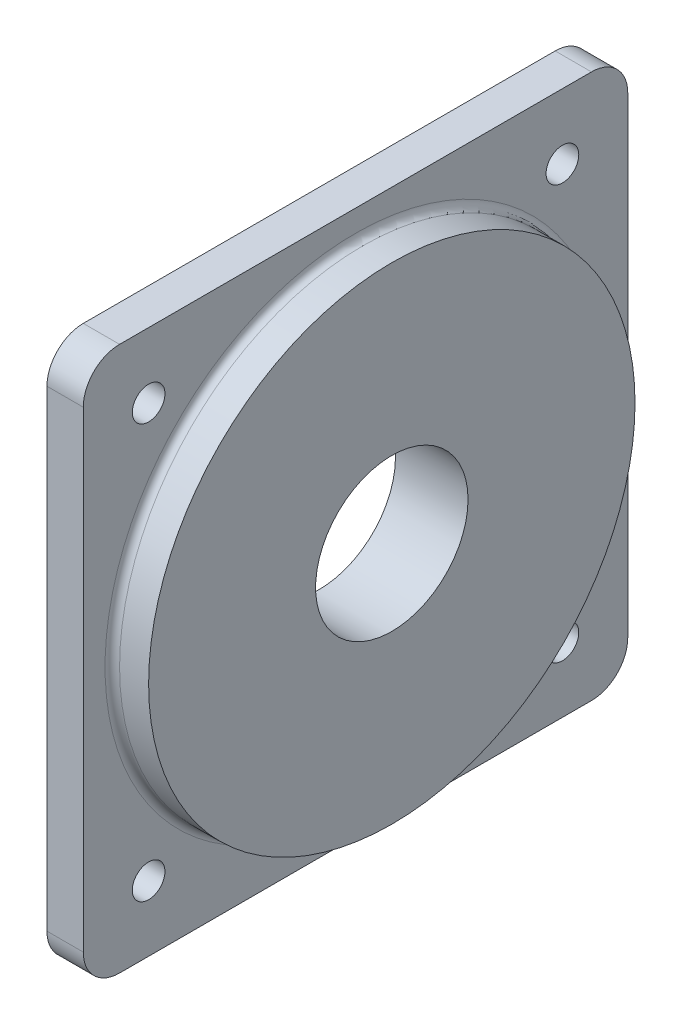
SolidWorks part; units mm, degrees
material "1060-H12"
ref_plane "Front" through (0, 0, 0) normal (0, 0, 1) x (1, 0, 0)
ref_plane "Top" through (0, 0, 0) normal (0, 1, 0) x (1, 0, 0)
ref_plane "Right" through (0, 0, 0) normal (1, 0, 0) x (0, 0, -1)
sketch "Croquis1" plane through (0, 0, 0) normal (1, 0, 0) x (0, 0, -1)
  line L1 (-75, 75) -> (75, 75)
  line L2 (-75, 75) -> (-75, -75)
  line L3 (-75, -75) -> (75, -75)
  line L4 (75, 75) -> (75, -75)
  line L5 (-75, 75) -> (75, -75) construction
  line L6 (-75, -75) -> (75, 75) construction
  point P0 (0, 0)
extrude "Saliente-Extruir1" add sketch "Croquis1" along normal blind 10
sketch "Croquis2" plane through (10, 0, 0) normal (1, 0, 0) x (0, 0, -1)
  circle A0 centre (0, 0) radius 67
  dimension "D1" = 134
extrude "Saliente-Extruir2" add sketch "Croquis2" along normal blind 10
fillet "Redondeo1" radius 10 4 edges at (5, -75, 75) (5, -75, -75) (5, 75, -75) (5, 75, 75)
fillet "Redondeo2" radius 2 1 edges at (10, 0, -67)
sketch "Croquis3" plane through (20, 0, 0) normal (1, 0, 0) x (0, 0, -1)
  line L0 (57, 0) -> (-57, 0) construction
  line L1 (57, -57) -> (-57, -57) construction
  line L2 (57, -57) -> (57, 57) construction
  line L3 (57, 57) -> (-57, 57) construction
  line L4 (-57, -57) -> (-57, 57) construction
  line L5 (57, -57) -> (-57, 57) construction
  line L6 (57, 57) -> (-57, -57) construction
  line L7 (-57, 0) -> (0, -57) construction
  line L8 (0, -57) -> (0, 57) construction
  circle A0 centre (0, 0) radius 21
  dimension "D1" = 42
  dimension "D2" = 114
extrude "Cortar-Extruir1" cut sketch "Croquis3" against normal through all
hole_wizard "Taladro de margen para M81" positions "Croquis4" profile "Croquis5" hole size "M8" standard "Ansi Metric" end condition through all
sketch "Croquis4" plane through (10, -7.4173, 252.7608) normal (1, 0, 0) x (0, 0, -1)
  line L0 (252.7608, 7.4173) -> (252.7608, 64.4173) construction
  point P0 (195.7608, 64.4173)
  point P2 (309.7608, 64.4173)
sketch "Croquis5" plane through (10, 57, 57) normal (0, 1, 0) x (0, 0, -1)
  line L0 (0, 0) -> (0, 10)
  line L1 (0, 10) -> (4.5, 10)
  line L2 (4.5, 10) -> (4.5, 0)
  line L3 (4.5, 0) -> (0, 0)
  line L4 (0, -6.35) -> (0, 107.95) construction
  dimension "Diámetro de taladro hasta el siguiente" = 9
  dimension "Profundidad de taladro hasta el siguiente" = 10
hole_wizard "Taladro de margen para M82" positions "Croquis6" profile "Croquis7" hole size "M8" standard "Ansi Metric" end condition through all
sketch "Croquis6" plane through (10, -7.4173, 252.7608) normal (1, 0, 0) x (0, 0, -1)
  point P0 (309.7608, -49.5827)
  point P2 (195.7608, -49.5827)
sketch "Croquis7" plane through (10, -57, -57) normal (0, 1, 0) x (0, 0, -1)
  line L0 (0, 0) -> (0, 10)
  line L1 (0, 10) -> (4.5, 10)
  line L2 (4.5, 10) -> (4.5, 0)
  line L3 (4.5, 0) -> (0, 0)
  line L4 (0, -6.35) -> (0, 107.95) construction
  dimension "Diámetro de taladro hasta el siguiente" = 9
  dimension "Profundidad de taladro hasta el siguiente" = 10
